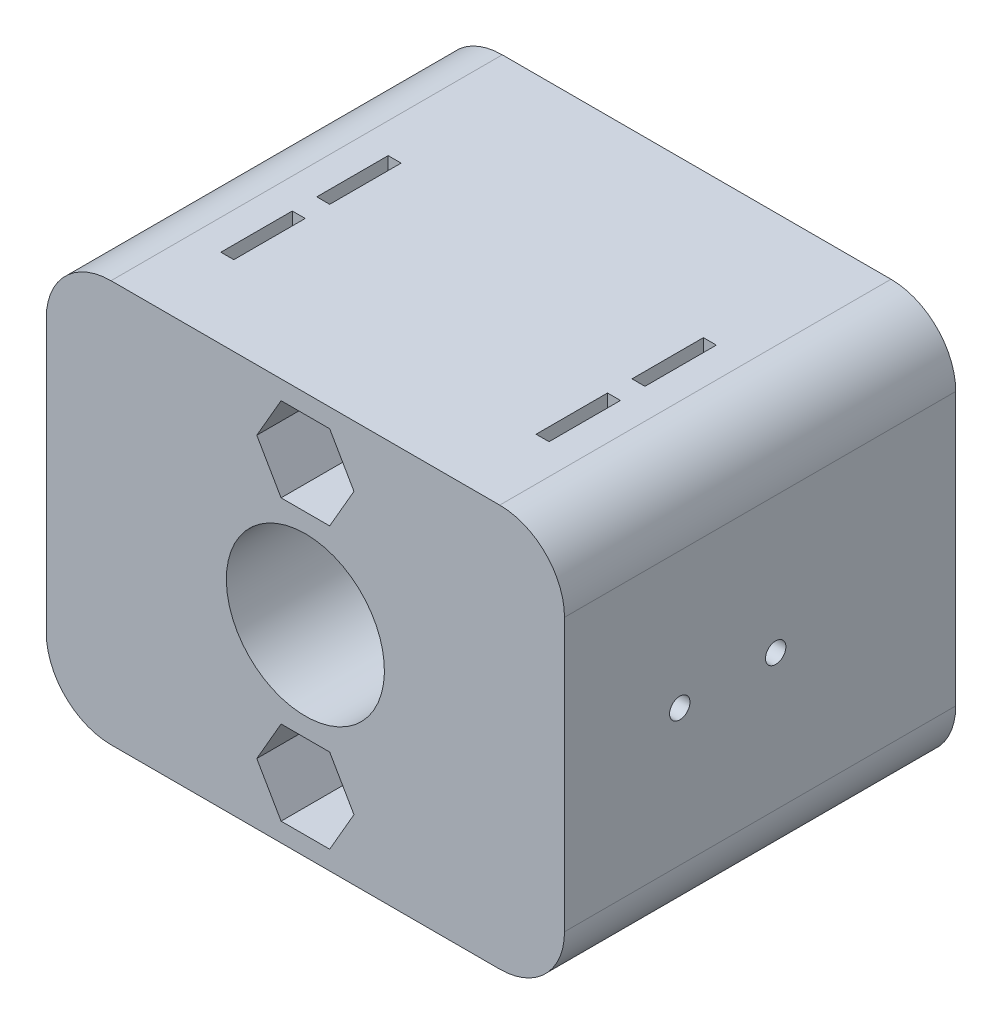
SolidWorks part; units mm, degrees
ref_plane "Front Plane" through (0, 0, 0) normal (0, 0, 1) x (1, 0, 0)
ref_plane "Top Plane" through (0, 0, 0) normal (0, 1, 0) x (1, 0, 0)
ref_plane "Right Plane" through (0, 0, 0) normal (1, 0, 0) x (0, 0, -1)
sketch "Sketch1" plane through (0, 0, 0) normal (0, 0, 1) x (1, 0, 0)
  line L0 (-82.55, -139.7) -> (-82.55, 139.7) construction
  line L1 (-82.55, 29.2453) -> (-31.75, 29.2453)
  line L2 (-82.55, 29.2453) -> (-82.55, -10.15)
  line L3 (-82.55, -10.15) -> (-31.75, -10.15)
  line L4 (-31.75, 29.2453) -> (-31.75, -10.15)
  line L5 (-82.55, 29.2453) -> (-31.75, -10.15) construction
  line L6 (-82.55, -10.15) -> (-31.75, 29.2453) construction
  line L7 (-31.75, -139.7) -> (-31.75, 139.7) construction
  arc A0 (-49.53, -8.6164) -> (-43.6698, -4.8149) centre (-57.15, 9.5476) ccw construction
  arc A1 (-64.77, 27.7117) -> (-70.6302, 23.9102) centre (-57.15, 9.5476) ccw construction
  circle A2 centre (-57.15, 23.27) radius 2.75
  circle A3 centre (-57.15, -4.1747) radius 2.75
  circle A4 centre (-57.15, -4.1747) radius 2.75 construction
  circle A5 centre (-57.15, 9.5476) radius 7.747
  circle A6 centre (-57.15, 9.5476) radius 7.747 construction
  point P4 (-57.15, 9.5476)
extrude "Boss-Extrude1" add sketch "Sketch1" along normal up to surface (38.35 mm away) contours L4 L1 L2 L3 A3 A2 region at (-57.15, 28.6025, 0)
sketch "Sketch2" plane through (0, -10.15, 0) normal (0, -1, 0) x (-1, 0, 0)
  line L5 (44.45, -17.65) -> (38.95, -17.65) construction
  line L6 (71.965, -14.15) -> (73.235, -14.15)
  line L7 (42.335, -30.55) -> (41.065, -30.55)
  line L8 (42.335, -30.55) -> (42.335, -23.55)
  line L9 (42.335, -23.55) -> (41.065, -23.55)
  line L10 (41.065, -30.55) -> (41.065, -23.55)
  line L11 (42.335, -30.55) -> (41.065, -23.55) construction
  line L12 (42.335, -23.55) -> (41.065, -30.55) construction
  line L17 (20.2, -30.55) -> (5.2, -30.55) construction
  line L20 (41.065, -14.15) -> (42.335, -14.15)
  line L21 (41.065, -14.15) -> (41.065, -21.15)
  line L22 (41.065, -21.15) -> (42.335, -21.15)
  line L23 (42.335, -14.15) -> (42.335, -21.15)
  line L24 (41.065, -14.15) -> (42.335, -21.15) construction
  line L25 (41.065, -21.15) -> (42.335, -14.15) construction
  line L30 (71.965, -14.15) -> (71.965, -21.15)
  line L31 (71.965, -21.15) -> (73.235, -21.15)
  line L32 (73.235, -14.15) -> (73.235, -21.15)
  line L33 (71.965, -14.15) -> (73.235, -21.15) construction
  line L34 (71.965, -21.15) -> (73.235, -14.15) construction
  line L35 (73.235, -23.55) -> (71.965, -23.55)
  line L36 (73.235, -23.55) -> (73.235, -30.55)
  line L37 (73.235, -30.55) -> (71.965, -30.55)
  line L38 (71.965, -23.55) -> (71.965, -30.55)
  line L39 (73.235, -23.55) -> (71.965, -30.55) construction
  line L40 (73.235, -30.55) -> (71.965, -23.55) construction
  line L41 (38.95, -6.35) -> (38.95, -22.35) construction
  line L42 (44.45, -22.35) -> (44.45, -6.35) construction
  line L43 (5.2, -14.15) -> (20.2, -14.15) construction
  line L45 (5.2, -23.55) -> (20.2, -23.55) construction
  line L46 (69.85, -27.05) -> (75.35, -27.05) construction
  line L47 (75.35, -32) -> (75.35, 3.175) construction
  line L48 (69.85, 3.175) -> (69.85, -32) construction
  point P4 (72.6, -17.65)
  point P9 (41.7, -27.05)
  point P14 (72.6, -27.05)
  point P15 (69.85, -27.05)
  point P21 (41.7, -17.65)
  point P31 (41.7, -17.65)
  point P41 (72.6, -27.05)
  dimension "D1" = 1.27
extrude "Cut-Extrude1" cut sketch "Sketch2" against normal through all both and the other way through all contours L10 L7 L8 L9 | L32 L6 L30 L31 | L35 L38 L37 L36 | L23 L22 L21 L20 region at (-72.6, -10.15, 17.65) region at (-41.7, -10.15, 27.05) region at (-72.6, -10.15, 27.05)
sketch "Sketch3" plane through (-31.75, 0, 0) normal (1, 0, 0) x (0, 0, -1)
  line L0 (-23.55, 9.5476) -> (-30.55, 9.5476) construction
  line L1 (-30.55, 29.2453) -> (-30.55, -10.15) construction
  line L3 (-23.55, 29.2453) -> (-23.55, -10.15) construction
  line L4 (-38.35, -10.15) -> (-38.35, 29.2453) construction
  line L8 (-14.15, 29.2453) -> (-21.15, 29.2453) construction
  circle A0 centre (-27.05, 9.5476) radius 3.5
  circle A1 centre (-17.65, 9.5476) radius 1
  circle A3 centre (-27.05, 9.5476) radius 1
  point P7 (-27.05, 9.5476)
  point P10 (-19.0238, 9.5476)
  point P17 (-38.35, 9.5476)
  point P18 (-17.65, 29.2453)
  dimension "D1" = 2
extrude "Cut-Extrude2" cut sketch "Sketch3" against normal through all both and the other way through all contours A3 | A1
fillet "Fillet1" radius 6.35 4 edges at (-82.55, -10.15, 19.175) (-82.55, 29.2453, 19.175) (-31.75, -10.15, 19.175) (-31.75, 29.2453, 19.175)
sketch "Sketch4" plane through (0, 0, 38.35) normal (0, 0, 1) x (1, 0, 0)
  line L0 (24.6066, -147) -> (19.8434, -147) construction
  line L1 (-52.3869, 23.2692) -> (-54.7677, 27.3946)
  line L2 (-54.7677, 27.3946) -> (-59.5309, 27.3954)
  line L3 (-59.5309, 27.3954) -> (-61.9131, 23.2708)
  line L4 (-61.9131, 23.2708) -> (-59.5323, 19.1454)
  line L5 (-59.5323, 19.1454) -> (-54.7691, 19.1446)
  line L6 (-54.7691, 19.1446) -> (-52.3869, 23.2692)
  line L7 (-52.3869, -4.1747) -> (-54.7684, -0.0497)
  line L8 (-54.7684, -0.0497) -> (-59.5316, -0.0497)
  line L9 (-59.5316, -0.0497) -> (-61.9131, -4.1747)
  line L10 (-61.9131, -4.1747) -> (-59.5316, -8.2997)
  line L11 (-59.5316, -8.2997) -> (-54.7684, -8.2997)
  line L12 (-54.7684, -8.2997) -> (-52.3869, -4.1747)
  circle A0 centre (-57.15, 23.27) radius 4.125 construction
  circle A1 centre (-57.15, -4.1747) radius 4.125 construction
extrude "Cut-Extrude3" cut sketch "Sketch4" against normal blind 6.35 contours L2 L3 L4 L5 L6 L1 | L11 L12 L7 L8 L9 L10
